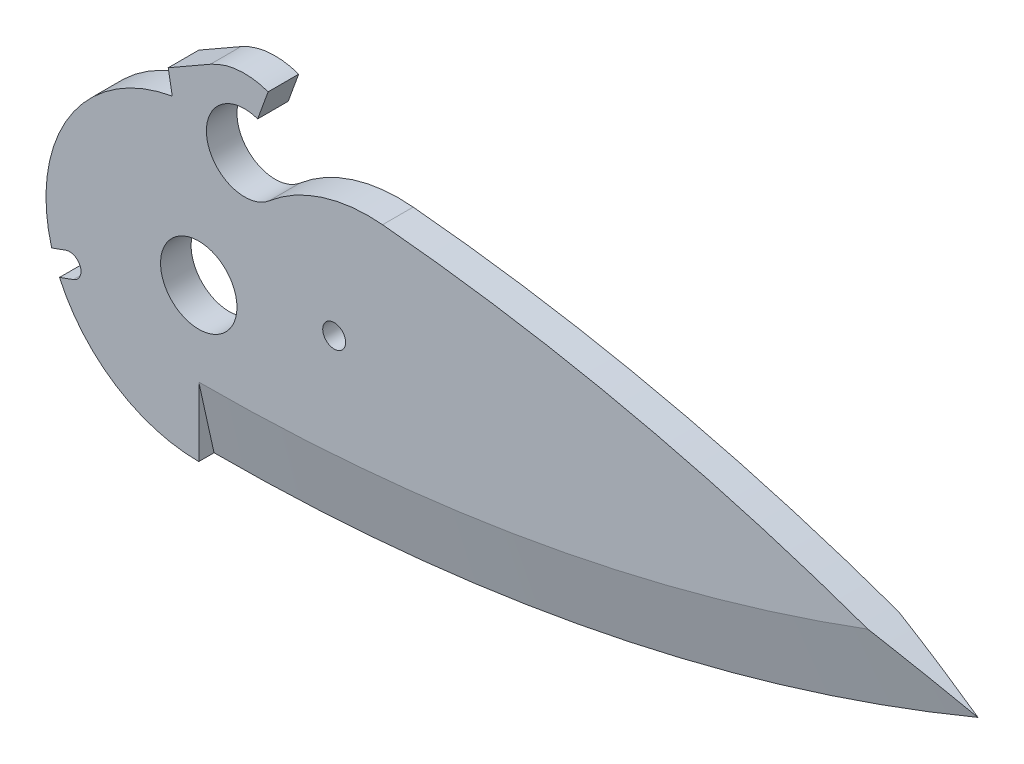
SolidWorks part; units mm, degrees
material "Obyčejná uhlíková ocel"
ref_plane "Přední rovina" through (0, 0, 0) normal (0, 0, 1) x (1, 0, 0)
ref_plane "Horní rovina" through (0, 0, 0) normal (0, 1, 0) x (1, 0, 0)
ref_plane "Pravá rovina" through (0, 0, 0) normal (1, 0, 0) x (0, 0, -1)
sketch "Skica1" plane through (0, 0, 0) normal (0, 0, 1) x (1, 0, 0)
  line L0 (0, 0) -> (28.9614, 0) construction
  line L1 (0.765, 12.9058) -> (-1.997, 11.3253)
  line L2 (-1.997, 11.3253) -> (-1.7365, 9.8481)
  line L3 (0, 10) -> (0, -10) construction
  line L4 (3, 9) -> (3, 16.5233) construction
  line L5 (3.8551, 11.3492) -> (4.5391, 13.2286)
  line L7 (0, 0) -> (58.3677, 0) construction
  line L8 (0, 0) -> (-0.0542, 0.0512) construction
  circle A0 centre (0, 0) radius 2.5
  arc A1 (-1.7365, 9.8481) -> (-10, 0) centre (0, 0) ccw
  arc A2 (12.0319, 9.442) -> (50, 0) centre (0, -120) cw
  arc A3 (0, -10) -> (50, 0) centre (0, 120) ccw
  arc A4 (3.8551, 11.3492) -> (4.6213, 7.097) centre (3, 9) ccw
  arc A5 (12.0319, 9.442) -> (4.6213, 7.097) centre (11.1064, -0.5151) ccw
  arc A6 (4.5391, 13.2286) -> (0.765, 12.9058) centre (3, 9) ccw
  arc A9 (-10, 0) -> (0, -10) centre (0, 0) ccw
  dimension "D1" = 10
  dimension "D2" = 5
  dimension "D3" = 60
  dimension "D5" = 2.5
  dimension "D6" = 2
  dimension "D8" = 10
  dimension "D11" = 10
  dimension "D12" = 0
  dimension "D4" = 3
  dimension "D7" = 20
  dimension "D9" = 1.5
  dimension "D10" = 9
extrude "Přidat vysunutím1" add sketch "Skica1" along normal mid plane 2
sketch "Skica4" plane through (0, 0, 0) normal (0, 0, 1) x (1, 0, 0)
  line L0 (0, 0) -> (8.8633, 1.5628) construction
  line L1 (0, 0) -> (27.9086, 0) construction
  line L2 (0, 0) -> (-8.4572, -3.0782) construction
  line L3 (-1.997, 11.3253) -> (-1.7365, 9.8481) construction
  line L4 (-8.7137, -2.3734) -> (-9.627, -2.7058)
  line L5 (-8.2007, -3.783) -> (-9.1139, -4.1153)
  circle A0 centre (8.8633, 1.5628) radius 0.75
  arc A1 (-8.2007, -3.783) -> (-8.7137, -2.3734) centre (-8.4572, -3.0782) ccw
  arc A2 (-1.7365, 9.8481) -> (0, -10) centre (0, 0) ccw construction
  arc A3 (-9.627, -2.7058) -> (-9.1139, -4.1153) centre (0, 0) ccw
  dimension "D2" = 1.5
  dimension "D1" = 9
  dimension "D3" = 10
  dimension "D4" = 100
extrude "Odebrat vysunutím1" cut sketch "Skica4" against normal through all and the other way through all
sketch "Skica2" plane through (0, 0, 0) normal (1, 0, 0) x (0, 0, -1)
  line L0 (0, -10) -> (1, -5.4893)
  line L1 (-1, -10) -> (1, -10) construction
  line L2 (1, -2.7058) -> (1, 9.8481) construction
  line L3 (0, -10) -> (0, -2.6677) construction
  line L4 (0, -10) -> (-1, -5.4893)
  line L5 (-1, -5.4893) -> (-1, -10)
  line L6 (-1, -10) -> (0, -10)
  line L7 (1, -5.4893) -> (1, -10)
  line L8 (1, -10) -> (0, -10)
  line L9 (0, -10) -> (0.0115, -9.9693)
  dimension "D1" = 25
sketch "Skica3" plane through (0, 0, 0) normal (0, 0, 1) x (1, 0, 0)
  arc A0 (0, -10) -> (50, 0) centre (0, 120) ccw construction
  arc A1 (0, -10) -> (50, 0) centre (0, 120) ccw
sweep "Odebrat tažením po křivce1" cut profiles "Skica2" path "Skica3"
mirror "Zrcadlit1" about plane through (0, 0, 0) normal (0, 0, 1) of "Odebrat tažením po křivce1"
sketch "Skica5" plane through (0, 0, -1) normal (0, 0, -1) x (-1, 0, 0)
  circle A0 centre (-13.6099, 7.7362) radius 0.9715
extrude "Přidat vysunutím2" [suppressed] add sketch "Skica5" along normal blind 2
